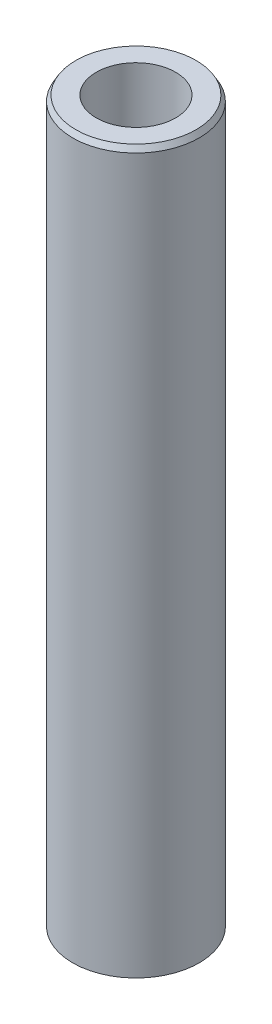
SolidWorks part; units mm, degrees
ref_plane "Front Plane" through (0, 0, 0) normal (0, 0, 1) x (1, 0, 0)
ref_plane "Top Plane" through (0, 0, 0) normal (0, 1, 0) x (1, 0, 0)
ref_plane "Right Plane" through (0, 0, 0) normal (1, 0, 0) x (0, 0, -1)
sketch "Sketch1" plane through (0, 0, 0) normal (0, 1, 0) x (1, 0, 0)
  circle A0 centre (0, 0) radius 52.5
  dimension "SHAFT_OD" = 105
extrude "Boss-Extrude1" add sketch "Sketch1" along normal blind 600
sketch "Sketch2" plane through (0, 0, 0) normal (0, 1, 0) x (1, 0, 0)
  circle A0 centre (0, 0) radius 32.9067
  dimension "BORE_D" = 65.8134
extrude "Cut-Extrude1" cut sketch "Sketch2" along normal through all
chamfer "Chamfer1" distance 4.5639 angle 30 2 edges at (0, 600, 52.5) (0, 0, 52.5) first distance on face at (0, 600, 52.5) first distance on face at (0, 0, 32.9067)
